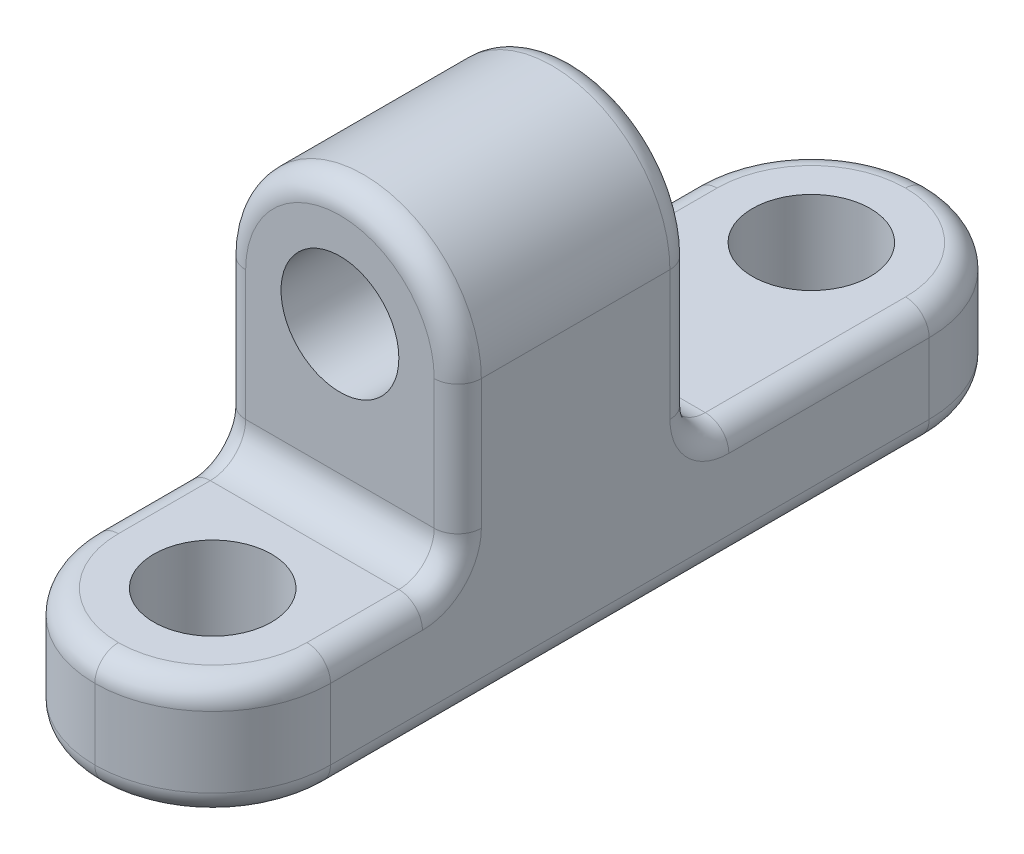
SolidWorks part; units mm, degrees
ref_plane "Front Plane" through (0, 0, 0) normal (0, 0, 1) x (1, 0, 0)
ref_plane "Top Plane" through (0, 0, 0) normal (0, 1, 0) x (1, 0, 0)
ref_plane "Right Plane" through (0, 0, 0) normal (1, 0, 0) x (0, 0, -1)
sketch "Sketch1" plane through (0, 0, 0) normal (0, 0, 1) x (1, 0, 0)
  line L0 (0, 0) -> (-10, 0) construction
  line L1 (-5, 0) -> (-5, -12)
  line L5 (5, 0) -> (5, -12)
  line L8 (5, -12) -> (-5, -12)
  line L9 (-5, -9) -> (5, -9)
  circle A0 centre (0, 0) radius 2.5
  arc A1 (5, 0) -> (-5, 0) centre (0, 0) ccw
  dimension "D1" = 5
  dimension "D2" = 5
  dimension "D3" = 12
  dimension "D4" = 3
extrude "Boss-Extrude1" add sketch "Sketch1" along normal blind 10 contours L0 A1 A0 | L5 L0 A0 L1 L9 | L9 L1 L8 L5 region at (0, -2.934, 0) region at (0, -10.5, 0)
sketch "Sketch2" plane through (0, -12, 0) normal (0, -1, 0) x (1, 0, 0)
  line L0 (5, 10) -> (-5, 10) construction
  line L2 (-5, 0) -> (5, 0)
  line L3 (-5, 0) -> (-5, -15)
  line L4 (-5, -15) -> (5, -15)
  line L5 (5, 0) -> (5, -15)
  line L6 (-5, 10) -> (5, 10)
  line L7 (-5, 10) -> (-5, 20.4)
  line L8 (-5, 20.4) -> (5, 20.4)
  line L9 (5, 10) -> (5, 20.4)
  circle A0 centre (0, -10) radius 2.5
  circle A1 centre (0, 15.4) radius 2.5
  point P4 (0, 5)
  point P17 (0, 0)
  dimension "D1" = 5
  dimension "D2" = 5
  dimension "D3" = 25.4
  dimension "D4" = 5
  dimension "D5" = 15
  dimension "D6" = 10
  dimension "D7" = 10
  dimension "D8" = 5
  dimension "D9" = 5
  dimension "D10" = 5
extrude "Boss-Extrude2" add sketch "Sketch2" against normal blind 5
fillet "Fillet1" radius 5 4 edges at (5, -9.5, -15) (5, -9.5, 20.4) (-5, -9.5, 20.4) (-5, -9.5, -15)
fillet "Fillet2" radius 1.5 2 edges at (0, -7, 10) (0, -7, 0)
fillet "Fillet3" radius 1 24 edges at (-3.5355, -12, 18.9355) (3.5355, -12, 18.9355) (5, -12, 2.7) (3.5355, -12, -13.5355) (-3.5355, -12, -13.5355) (-3.5355, -7, 18.9355) (3.5355, -7, 18.9355) (5, -7, 13.45) (5, -6.5607, 10.4393) (5, -2.75, 10) (0, 5, 10) (-5, -2.75, 10) (-5, -6.5607, 10.4393) (-5, -6.5607, -0.4393) (-5, -2.75, 0) (0, 5, 0) (5, -2.75, 0) (5, -6.5607, -0.4393) (5, -7, -5.75) (3.5355, -7, -13.5355) (-3.5355, -7, -13.5355) (-5, -12, 2.7) (-5, -7, 13.45) (-5, -7, -5.75)
